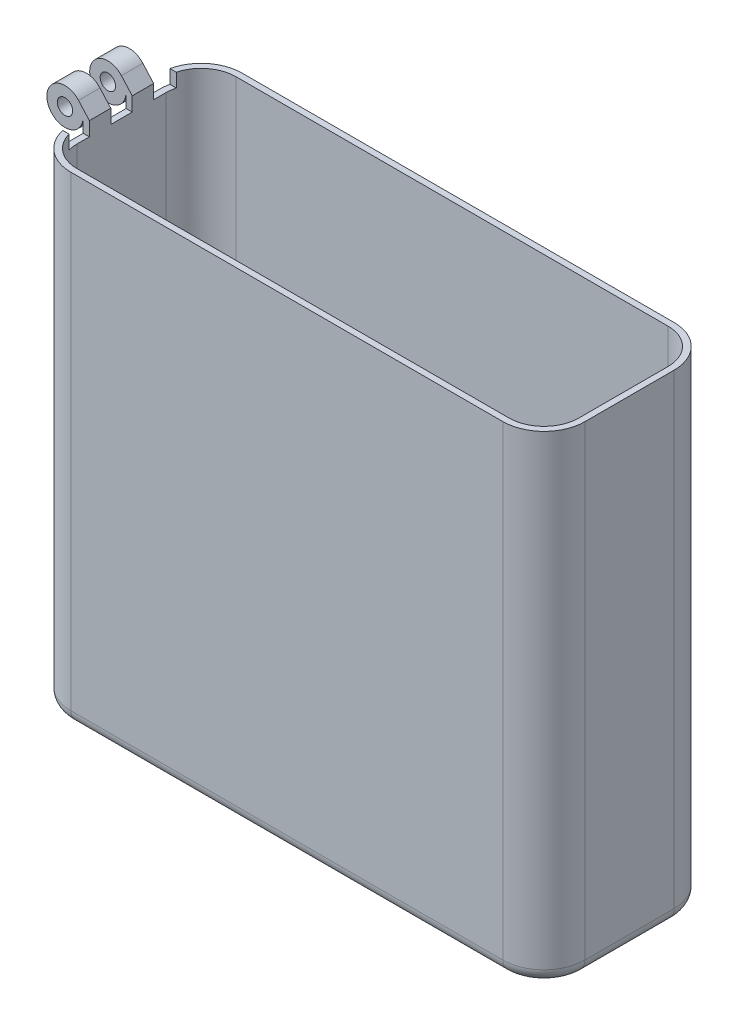
SolidWorks part; units mm, degrees
material "Chrome Stainless Steel"
ref_plane "Front Plane" through (0, 0, 0) normal (0, 0, 1) x (1, 0, 0)
ref_plane "Top Plane" through (0, 0, 0) normal (0, 1, 0) x (1, 0, 0)
ref_plane "Right Plane" through (0, 0, 0) normal (1, 0, 0) x (0, 0, -1)
sketch "Sketch1" plane through (0, 0, 0) normal (0, 0, 1) x (1, 0, 0)
  line L1 (0, 0) -> (38.1, 0)
  line L2 (0, 0) -> (0, 35.56)
  line L3 (0, 35.56) -> (38.1, 35.56)
  line L4 (38.1, 0) -> (38.1, 35.56)
  dimension "D1" = 38.1
  dimension "D2" = 35.56
extrude "Boss-Extrude1" add sketch "Sketch1" along normal mid plane 12.7
fillet "BOTTOM Fillet1" radius 1.016 4 edges at (0, 0, 0) (19.05, 0, -6.35) (38.1, 0, 0) (19.05, 0, 6.35) type face fillet first side face at (38.1, 17.78, 0) first side face at (19.05, 17.78, -6.35) first side face at (0, 17.78, 0) first side face at (19.05, 17.78, 6.35) second side face at (19.05, 0, 0)
fillet "Fillet2" radius 3.048 8 edges at (37.8024, 0.2976, -6.0524) (37.8024, 0.2976, 6.0524) (0.2976, 0.2976, -6.0524) (0.2976, 0.2976, 6.0524) (0, 18.288, 6.35) (0, 18.288, -6.35) (38.1, 18.288, 6.35) (38.1, 18.288, -6.35)
sketch "Sketch3" plane through (0, 0, 0) normal (-1, 0, 0) x (0, 0, 1)
  line L1 (-3.9688, 35.56) -> (3.9688, 35.56)
  line L2 (-3.9688, 35.56) -> (-3.9688, 34.544)
  line L3 (-3.9688, 34.544) -> (3.9688, 34.544)
  line L4 (3.9688, 35.56) -> (3.9688, 34.544)
  line L6 (3.302, 35.56) -> (-3.302, 35.56) construction
  point P6 (0, 35.56)
  point P7 (0, 35.56)
  dimension "D1" = 1.016
  dimension "D2" = 7.9375
extrude "Cut-Extrude3" cut sketch "Sketch3" against normal blind 12.7
sketch "Sketch5" plane through (0, 35.56, 0) normal (0, 1, 0) x (1, 0, 0)
  line L2 (37.6428, -3.302) -> (37.6428, 3.302)
  line L3 (0.4572, 3.302) -> (0.4572, -3.302)
  line L4 (0.4572, 3.302) -> (0.4572, -3.302)
  line L5 (35.052, 5.8928) -> (3.048, 5.8928)
  line L6 (0.0738, 3.9688) -> (12.7, 3.9688)
  line L7 (12.7, 3.9688) -> (12.7, -3.9688)
  line L8 (12.7, -3.9688) -> (0.0738, -3.9688)
  line L9 (3.048, -6.35) -> (35.052, -6.35)
  line L10 (38.1, -3.302) -> (38.1, 3.302)
  line L11 (35.052, 6.35) -> (3.048, 6.35)
  line L12 (0.0738, 3.9688) -> (12.7, 3.9688)
  line L13 (12.7, 3.9688) -> (12.7, -3.9688)
  line L14 (12.7, -3.9688) -> (0.0738, -3.9688)
  line L15 (3.048, -6.35) -> (35.052, -6.35)
  line L16 (38.1, -3.302) -> (38.1, 3.302)
  line L17 (35.052, 6.35) -> (3.048, 6.35)
  line L18 (3.048, -5.8928) -> (35.052, -5.8928)
  arc A4 (3.048, 6.35) -> (0.0738, 3.9688) centre (3.048, 3.302) ccw
  arc A5 (0.0738, -3.9688) -> (3.048, -6.35) centre (3.048, -3.302) ccw
  arc A6 (35.052, -6.35) -> (38.1, -3.302) centre (35.052, -3.302) ccw
  arc A7 (38.1, 3.302) -> (35.052, 6.35) centre (35.052, 3.302) ccw
  arc A8 (3.048, 6.35) -> (0.0738, 3.9688) centre (3.048, 3.302) ccw
  arc A9 (0.0738, -3.9688) -> (3.048, -6.35) centre (3.048, -3.302) ccw
  arc A10 (35.052, -6.35) -> (38.1, -3.302) centre (35.052, -3.302) ccw
  arc A11 (38.1, 3.302) -> (35.052, 6.35) centre (35.052, 3.302) ccw
  arc A12 (37.6428, 3.302) -> (35.052, 5.8928) centre (35.052, 3.302) ccw
  arc A13 (3.048, 5.8928) -> (0.5199, 3.8687) centre (3.048, 3.302) ccw
  arc A14 (0.4572, -3.302) -> (0.5199, -3.8687) centre (3.048, -3.302) ccw
  arc A15 (0.5199, 3.8687) -> (0.4572, 3.302) centre (3.048, 3.302) ccw
  arc A16 (0.4572, -3.302) -> (0.5199, -3.8687) centre (3.048, -3.302) ccw
  arc A17 (0.5199, 3.8687) -> (0.4572, 3.302) centre (3.048, 3.302) ccw
  arc A18 (0.5199, -3.8687) -> (3.048, -5.8928) centre (3.048, -3.302) ccw
  arc A19 (35.052, -5.8928) -> (37.6428, -3.302) centre (35.052, -3.302) ccw
  line M16 (12.7, 3.9688) -> (12.7, -3.9688)
  line M17 (12.7, -3.9688) -> (0.0738, -3.9688)
  dimension "D1" = 0
  dimension "D2" = 0.4572
  dimension "D3" = 0.4572
  dimension "D4" = 0.4572
extrude "Cut-Extrude4" cut sketch "Sketch5" against normal blind 34.4678 contours A16 A18 L12 A13 A17 L4 M17 M16 region at (6.581, 35.56, 0)
sketch "Sketch7" plane through (0, 35.56, 0) normal (0, 1, 0) x (1, 0, 0)
  line L2 (3.048, -5.8928) -> (35.052, -5.8928)
  line L3 (0.4572, 3.302) -> (0.4572, -3.302)
  line L4 (0.4572, 3.302) -> (0.4572, -3.302)
  line L5 (37.6428, -3.302) -> (37.6428, 3.302)
  line L6 (35.052, 5.8928) -> (3.048, 5.8928)
  line L10 (0.0738, 3.9688) -> (12.7, 3.9688)
  line L11 (12.7, 3.9688) -> (12.7, -3.9688)
  line L12 (12.7, -3.9688) -> (0.0738, -3.9688)
  line L13 (3.048, -6.35) -> (35.052, -6.35)
  line L14 (38.1, -3.302) -> (38.1, 3.302)
  line L15 (35.052, 6.35) -> (3.048, 6.35)
  line L19 (3.048, -6.35) -> (35.052, -6.35)
  line L20 (38.1, -3.302) -> (38.1, 3.302)
  line L21 (35.052, 6.35) -> (3.048, 6.35)
  arc A2 (0.5199, 3.8687) -> (0.4572, 3.302) centre (3.048, 3.302) ccw
  arc A3 (0.5199, 3.8687) -> (0.4572, 3.302) centre (3.048, 3.302) ccw
  arc A4 (0.5199, -3.8687) -> (3.048, -5.8928) centre (3.048, -3.302) ccw
  arc A5 (0.4572, -3.302) -> (0.5199, -3.8687) centre (3.048, -3.302) ccw
  arc A6 (3.048, 6.35) -> (0.0738, 3.9688) centre (3.048, 3.302) ccw
  arc A7 (0.0738, -3.9688) -> (3.048, -6.35) centre (3.048, -3.302) ccw
  arc A8 (35.052, -6.35) -> (38.1, -3.302) centre (35.052, -3.302) ccw
  arc A9 (38.1, 3.302) -> (35.052, 6.35) centre (35.052, 3.302) ccw
  arc A11 (0.0738, -3.9688) -> (3.048, -6.35) centre (3.048, -3.302) ccw
  arc A12 (35.052, -6.35) -> (38.1, -3.302) centre (35.052, -3.302) ccw
  arc A13 (38.1, 3.302) -> (35.052, 6.35) centre (35.052, 3.302) ccw
  arc A14 (0.4572, -3.302) -> (0.5199, -3.8687) centre (3.048, -3.302) ccw
  arc A15 (35.052, -5.8928) -> (37.6428, -3.302) centre (35.052, -3.302) ccw
  arc A16 (37.6428, 3.302) -> (35.052, 5.8928) centre (35.052, 3.302) ccw
  arc A17 (3.048, 5.8928) -> (0.5199, 3.8687) centre (3.048, 3.302) ccw
  arc A22 (3.048, 6.35) -> (0.0738, 3.9688) centre (3.048, 3.302) ccw construction
  line M15 (0.0738, 3.9688) -> (12.7, 3.9688)
  line M16 (12.7, 3.9688) -> (12.7, -3.9688)
  line M17 (12.7, -3.9688) -> (0.0738, -3.9688)
  dimension "D1" = 0
  dimension "D2" = 0.4572
  dimension "D3" = 0.4572
extrude "Cut-Extrude5" cut sketch "Sketch7" against normal blind 34.4678 contours L6 A17 A4 L2 A15 L5 A16 M15 M16 M17 region at (22.6618, 35.56, 0)
sketch "Sketch8" plane through (0, 35.56, 0) normal (0, 1, 0) x (1, 0, 0)
  line L0 (0, 2.3813) -> (0, 0.7938)
  line L17 (0, 3.302) -> (0, -3.302) construction
  line L18 (-1.3462, 3.0791) -> (-1.3462, -3.4259) construction
  line L20 (-1.3462, 2.3813) -> (-1.3462, 0.7938)
  line L21 (-1.3462, 2.3813) -> (0, 2.3813)
  line L22 (-1.3462, 0.7938) -> (0, 0.7938)
  line L24 (0, -2.3812) -> (0, -0.7937)
  line L25 (-1.3462, -0.7938) -> (0, -0.7937)
  line L26 (-1.3462, -2.3813) -> (-1.3462, -0.7938)
  line L27 (-1.3462, -2.3813) -> (0, -2.3812)
  dimension "D1" = 1.3462
  dimension "D2" = 1.5875
sketch "Sketch10" plane through (0, 0, 0) normal (0, -1, 0) x (1, 0, 0)
  text T0 "\r\nBRADFORD.PA. MADE IN U.S.A." font "Century Gothic" height 1.651
  text T1 "Zippo"
extrude "Cut-Extrude8" cut sketch "Sketch10" against normal blind 0.254
ref_plane "Plane1" through (0, 35.56, 0) normal (0, 1, 0) x (1, 0, 0)
sketch "Sketch13" plane through (0, 0, 0) normal (-1, 0, 0) x (0, 0, 1)
  line L0 (-3.302, 34.544) -> (3.302, 34.544) construction
  line L1 (-2.3813, 34.544) -> (-0.7938, 34.544)
  line L2 (-2.3813, 34.544) -> (-2.3813, 35.56)
  line L3 (-2.3813, 35.56) -> (-0.7938, 35.56)
  line L4 (-0.7938, 34.544) -> (-0.7938, 35.56)
  line L6 (-2.3813, 35.56) -> (-0.7938, 35.56) construction
  line L7 (-2.3813, 35.56) -> (-0.7938, 35.56) construction
  line L9 (0.7937, 35.56) -> (2.3812, 35.56)
  line L10 (0.7937, 35.56) -> (0.7937, 34.544)
  line L11 (0.7937, 34.544) -> (2.3812, 34.544)
  line L12 (2.3812, 35.56) -> (2.3812, 34.544)
extrude "Boss-Extrude4" add sketch "Sketch13" against normal blind 0.4572
sketch "Sketch17" plane through (0, 0, -2.3813) normal (0, 0, -1) x (-1, 0, 0)
  line L0 (0, 35.5854) -> (1.3462, 35.5854) construction
  line L1 (-0.4572, 35.56) -> (0, 35.56)
  line L2 (-0.4572, 35.56) -> (-0.4572, 35.5854)
  line L3 (-0.4572, 35.5854) -> (0, 35.5854) construction
  line L4 (0, 35.56) -> (0, 35.5854)
  line L5 (-0.4572, 35.5854) -> (0.3413, 36.4812)
  arc A2 (0, 35.5854) -> (0.3413, 36.4812) centre (1.3462, 35.5854) ccw
  circle A3 centre (1.3462, 35.5854) radius 0.5715
  dimension "D3" = 2.6924
  dimension "D4" = 1.143
  dimension "D1" = 0.4572
  dimension "D2" = 0.0254
extrude "Boss-Extrude6" add sketch "Sketch17" against normal blind 1.5875
sketch "Sketch18" plane through (0, 0, 2.3813) normal (0, 0, 1) x (1, 0, 0)
  line L0 (-0.0018, 35.5854) -> (-1.348, 35.5854) construction
  line L1 (0.4572, 35.56) -> (-0.0018, 35.56)
  line L2 (0.4572, 35.56) -> (0.4572, 35.5854)
  line L3 (0.4572, 35.5854) -> (-0.0018, 35.5854) construction
  line L4 (-0.0018, 35.56) -> (-0.0018, 35.5854)
  line L5 (0.4572, 35.5854) -> (-0.3442, 36.4823)
  arc A0 (-0.3442, 36.4823) -> (-0.0018, 35.5854) centre (-1.348, 35.5854) ccw
  circle A1 centre (-1.348, 35.5854) radius 0.5715
  dimension "D1" = 2.6924
  dimension "D2" = 1.143
  dimension "D3" = 0.0254
extrude "Boss-Extrude7" add sketch "Sketch18" against normal blind 1.5875
